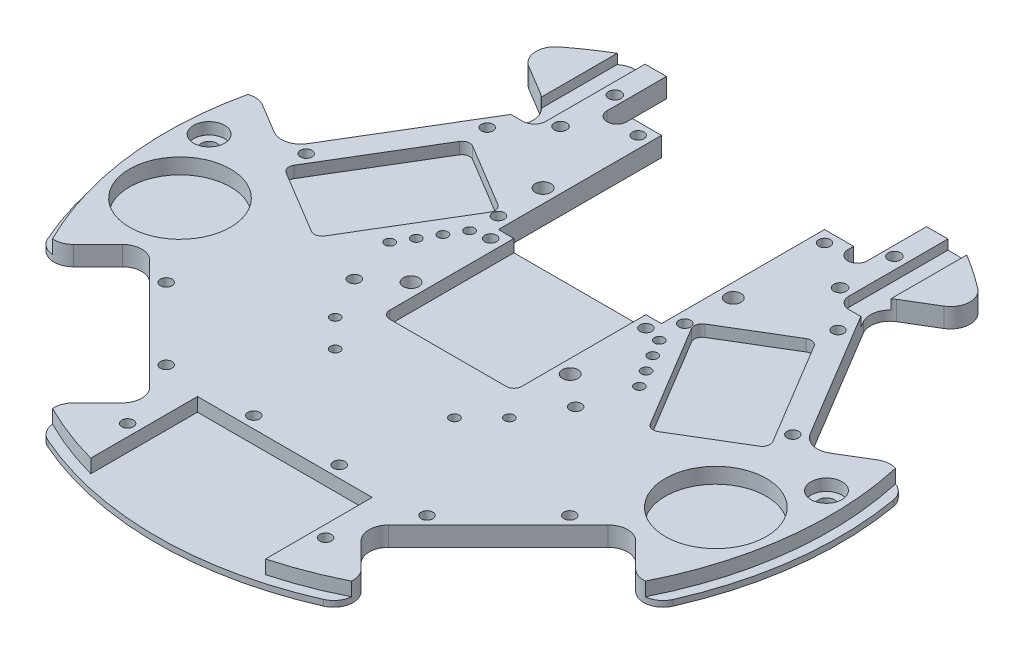
SolidWorks part; units mm, degrees
material "7079 Alloy"
ref_plane "Front" through (0, 0, 0) normal (0, 0, 1) x (1, 0, 0)
ref_plane "Top" through (0, 0, 0) normal (0, 1, 0) x (1, 0, 0)
ref_plane "Right" through (0, 0, 0) normal (1, 0, 0) x (0, 0, -1)
sketch "Sketch1" plane through (0, 0, 0) normal (0, 1, 0) x (1, 0, 0)
  line L0 (0, 0) -> (88, 0)
  line L1 (0, 88) -> (0, 0)
  line L2 (-88, 0) -> (0, 0)
  line L3 (0, -88) -> (0, 0)
  line L4 (0, 0) -> (62.2254, -62.2254)
  line L5 (0, 0) -> (-62.2254, -62.2254)
  line L6 (0, 0) -> (75.4307, 45.3234)
  line L7 (0, 0) -> (-75.4307, 45.3234)
  line L8 (59.4468, 64.8851) -> (41.5542, 54.1341)
  line L9 (41.5542, 54.1341) -> (67.3061, 11.2757)
  line L10 (67.3061, 11.2757) -> (85.1987, 22.0267)
  line L11 (77.3392, -41.9839) -> (62.579, -27.2236)
  line L12 (62.579, -27.2236) -> (27.2236, -62.579)
  line L13 (27.2236, -62.579) -> (41.9839, -77.3392)
  line L14 (-41.9839, -77.3392) -> (-27.2236, -62.579)
  line L15 (-27.2236, -62.579) -> (-62.579, -27.2236)
  line L16 (-62.579, -27.2236) -> (-77.3392, -41.9839)
  line L17 (-85.1987, 22.0267) -> (-67.3061, 11.2757)
  line L18 (-67.3061, 11.2757) -> (-41.5542, 54.1341)
  line L19 (-41.5542, 54.1341) -> (-59.4468, 64.8851)
  line L20 (-59.4468, 64.8851) -> (7.3885, 64.8851)
  line L21 (7.3885, 64.8851) -> (59.4468, 64.8851)
  line L22 (-41.5542, 54.1341) -> (0, 54.1341)
  line L23 (0, 54.1341) -> (41.5542, 54.1341)
  line L24 (41.5542, 54.1341) -> (41.5542, 77.5709)
  line L25 (-41.5542, 77.5709) -> (0, 77.5709)
  line L26 (-41.5542, 77.5709) -> (-41.5542, 54.1341)
  line L27 (0, 77.5709) -> (41.5542, 77.5709)
  circle A0 centre (0, 0) radius 88
  dimension "D1" = 176
  dimension "D2" = 31
  dimension "D3" = 31
  dimension "D4" = 45
  dimension "D5" = 24.5
  dimension "D6" = 24.5
  dimension "D7" = 24.5
  dimension "D8" = 24.5
  dimension "D9" = 25
  dimension "D10" = 25
  dimension "D11" = 25
  dimension "D12" = 25
  dimension "D13" = 25
  dimension "D14" = 25
  dimension "D15" = 25
  dimension "D16" = 25
sketch "Sketch2" plane through (0, 0, 0) normal (0, 1, 0) x (1, 0, 0)
  line L0 (85.1987, 22.0267) -> (67.3061, 11.2757)
  line L1 (67.3061, 11.2757) -> (41.5542, 54.1341)
  line L2 (77.3392, -41.9839) -> (62.579, -27.2236)
  line L3 (62.579, -27.2236) -> (27.2236, -62.579)
  line L4 (27.2236, -62.579) -> (41.9839, -77.3392)
  line L5 (-41.9839, -77.3392) -> (-27.2236, -62.579)
  line L6 (-27.2236, -62.579) -> (-62.579, -27.2236)
  line L7 (-62.579, -27.2236) -> (-77.3392, -41.9839)
  line L8 (-85.1987, 22.0267) -> (-67.3061, 11.2757)
  line L9 (-67.3061, 11.2757) -> (-41.5542, 54.1341)
  line L10 (-43, 76.7789) -> (43, 76.7789)
  line L15 (-41.5542, 54.1341) -> (-59.4468, 64.8851)
  line L16 (0, 0) -> (0, 111.6496) construction
  line L17 (41.5542, 54.1341) -> (59.4468, 64.8851)
  line L18 (-43, 76.7789) -> (43, 76.7789) construction
  arc A0 (85.1987, 22.0267) -> (77.3392, -41.9839) centre (0, 0) cw
  arc A1 (41.9839, -77.3392) -> (-41.9839, -77.3392) centre (0, 0) cw
  arc A2 (-77.3392, -41.9839) -> (-85.1987, 22.0267) centre (0, 0) cw
  arc A3 (-43, 76.7789) -> (-59.4468, 64.8851) centre (0, 0) ccw
  arc A4 (59.4468, 64.8851) -> (43, 76.7789) centre (0, 0) ccw
  dimension "D2" = 86
extrude "Extrude1" add sketch "Sketch2" against normal blind 5
sketch "Sketch3" plane through (0, 0, 0) normal (0, 1, 0) x (1, 0, 0)
  line L0 (-21, 76.7789) -> (-21, 21)
  line L1 (-21, 21) -> (21, 21)
  line L2 (21, 21) -> (21, 76.7789)
  line L3 (43, 76.7789) -> (-43, 76.7789) construction
  line L5 (-21, 76.7789) -> (21, 76.7789)
  dimension "D1" = 21
  dimension "D2" = 21
  dimension "D3" = 21
extrude "Extrude2" cut sketch "Sketch3" against normal up to surface (5 mm away) up to face at (0, -5, -1.5971)
sketch "Sketch4" plane through (0, 0, 0) normal (0, 1, 0) x (-1, 0, 0)
  line L0 (17, 13) -> (17, -27)
  line L2 (17, 13) -> (-17, 13)
  line L3 (17, -27) -> (-17, -27)
  line L4 (-17, -27) -> (-17, 13)
  line L5 (21, -21) -> (-21, -21) construction
  dimension "D1" = 34
  dimension "D2" = 17
  dimension "D3" = 34
  dimension "D4" = 40
extrude "Extrude3" cut sketch "Sketch4" against normal blind 3.2
sketch "Sketch5" plane through (0, 0, 0) normal (0, 1, 0) x (1, 0, 0)
  line L0 (42.9633, -4.5175) -> (62.6781, 7.3283)
  line L1 (62.6781, 7.3283) -> (44.6518, 37.3292)
  line L2 (44.6518, 37.3292) -> (24.9369, 25.4833)
  line L3 (24.9369, 25.4833) -> (42.9633, -4.5175)
  line L5 (67.3061, 11.2757) -> (41.5542, 54.1341) construction
  line L6 (85.1987, 22.0267) -> (67.3061, 11.2757) construction
  dimension "D1" = 6
  dimension "D2" = 35
  dimension "D3" = 23
  dimension "D4" = 1
extrude "Extrude4" cut sketch "Sketch5" against normal blind 3
mirror "Mirror1" about plane through (0, 0, 0) normal (1, 0, 0) of "Extrude4"
sketch "Sketch6" plane through (0, 0, 0) normal (0, 1, 0) x (1, 0, 0)
  line L0 (0, 0) -> (75.4307, 45.3234) construction
  line L1 (41.5542, 54.1341) -> (67.3061, 11.2757) construction
  line L2 (62.579, -27.2236) -> (27.2236, -62.579) construction
  line L3 (0, 0) -> (62.2254, -62.2254) construction
  circle A0 centre (45.1631, 42.303) radius 1.5
  circle A1 centre (62.6744, 13.1593) radius 1.5
  circle A2 centre (51.9723, -33.5876) radius 1.5
  circle A3 centre (33.5876, -51.9723) radius 1.5
  dimension "D1" = 3
  dimension "D2" = 3
  dimension "D3" = 3
  dimension "D4" = 3
  dimension "D6" = 3
  dimension "D8" = 3
  dimension "D9" = 3
  dimension "D10" = 13
  dimension "D11" = 13
  dimension "D12" = 3
  dimension "D5" = 13
  dimension "D7" = 21
extrude "Extrude5" cut sketch "Sketch6" against normal up to surface (5 mm away) up to face at (0, -5, -10.1957)
mirror "Mirror2" about plane through (0, 0, 0) normal (1, 0, 0) of "Extrude5"
sketch "Sketch7" plane through (0, 0, 0) normal (0, 1, 0) x (-1, 0, 0)
  line L1 (-21, -21) -> (-21, -76.7789) construction
  line L2 (-17, -21) -> (-21, -21) construction
  circle A0 centre (-24, -60) radius 1.5
  circle A1 centre (-24, -24) radius 1.5
  dimension "D2" = 3
  dimension "D3" = 3
  dimension "D4" = 3
  dimension "D5" = 3
  dimension "D6" = 3
  dimension "D1" = 36
extrude "Extrude6" cut sketch "Sketch7" against normal up to surface (5 mm away) up to face at (-51.9723, -5, 32.0876)
mirror "Mirror3" about plane through (0, 0, 0) normal (1, 0, 0) of "Extrude6"
sketch "Sketch8" plane through (0, 0, 0) normal (0, 1, 0) x (1, 0, 0)
  line L0 (33.5, 68.7344) -> (33.5, 63)
  line L6 (33.5, 63) -> (21, 63)
  line L7 (21, 21) -> (21, 76.7789) construction
  line L8 (21, 63) -> (21, 76.7789)
  line L9 (21, 76.7789) -> (33.5, 76.7789)
  line L10 (43, 76.7789) -> (21, 76.7789) construction
  line L11 (33.5, 76.7789) -> (33.5, 68.7344)
  circle A0 centre (24, 60) radius 1.5 construction
  dimension "D4" = 3
extrude "Extrude7" cut sketch "Sketch8" against normal up to surface (5 mm away) up to face at (-24, -5, -61.5)
mirror "Mirror4" about plane through (0, 0, 0) normal (1, 0, 0) of "Extrude7"
sketch "Sketch9" plane through (0, 0, 0) normal (0, 1, 0) x (1, 0, 0)
  line L5 (33.5, 63) -> (33.5, 76.7789) construction
  circle A0 centre (36, 66) radius 1.6
  circle A1 centre (36, 52) radius 1.6
  dimension "D1" = 3.2
  dimension "D2" = 3.2
  dimension "D3" = 52
  dimension "D4" = 66
  dimension "D5" = 2.5
extrude "Extrude8" cut sketch "Sketch9" against normal up to surface (5 mm away) up to face at (-24, -5, -61.5)
mirror "Mirror5" about plane through (0, 0, 0) normal (1, 0, 0) of "Extrude8"
fillet "Fillet2" radius 2 10 edges at (-17, -1.6, 13) (17, -1.6, 13) (-42.9633, -1.5, 4.5175) (-24.9369, -1.5, -25.4833) (-44.6518, -1.5, -37.3292) (-62.6781, -1.5, -7.3283) (42.9633, -1.5, 4.5175) (24.9369, -1.5, -25.4833) (44.6518, -1.5, -37.3292) (62.6781, -1.5, -7.3283)
fillet "Fillet3" radius 5 16 edges at (59.4468, -2.5, -64.8851) (41.5542, -2.5, -54.1341) (67.3061, -2.5, -11.2757) (85.1987, -2.5, -22.0267) (77.3392, -2.5, 41.9839) (62.579, -2.5, 27.2236) (27.2236, -2.5, 62.579) (41.9839, -2.5, 77.3392) (-27.2236, -2.5, 62.579) (-41.9839, -2.5, 77.3392) (-62.579, -2.5, 27.2236) (-77.3392, -2.5, 41.9839) (-85.1987, -2.5, -22.0267) (-67.3061, -2.5, -11.2757) (-41.5542, -2.5, -54.1341) (-59.4468, -2.5, -64.8851)
fillet "Fillet4" radius 5 2 edges at (43, -2.5, -76.7789) (-43, -2.5, -76.7789)
sketch "Sketch11" plane through (0, 0, 0) normal (0, 1, 0) x (1, 0, 0)
  line L3 (-21, 21) -> (-21, 63) construction
  line L4 (21, 21) -> (21, 63) construction
  circle A2 centre (24.5, 36) radius 2
  circle A3 centre (-24.5, 36) radius 2
  dimension "D7" = 4
  dimension "D8" = 4
  dimension "D9" = 3.5
  dimension "D10" = 3.5
extrude "Extrude10" cut sketch "Sketch11" against normal up to surface (5 mm away) up to face at (-36, -5, -67.6)
sketch "Sketch14" plane through (0, 0, 0) normal (0, 1, 0) x (1, 0, 0)
  line L0 (25.967, 23.769) -> (41.9332, -2.8032) construction
  line L1 (42.9374, 36.2991) -> (26.6513, 26.5134) construction
  line L2 (25.967, 23.769) -> (41.9332, -2.8032) construction
  line L5 (64.7309, 15.5616) -> (44.1294, 49.8483) construction
  line L6 (30.7591, -59.0434) -> (59.0434, -30.7591) construction
  line L7 (66.1145, -30.7591) -> (72.3997, -37.0444) construction
  circle A0 centre (24.4364, 17.0161) radius 1.25
  circle A1 centre (29.5867, 8.4444) radius 1.25
  circle A2 centre (22.4224, -19.5939) radius 1.25
  circle A3 centre (15.3513, -26.665) radius 1.25
  circle A4 centre (27.0116, 12.7303) radius 1.25
  circle A5 centre (32.1619, 4.1586) radius 1.25
  dimension "D1" = 2.5
  dimension "D3" = 7
  dimension "D4" = 2.5
  dimension "D7" = 33.79
  dimension "D9" = 2.5
  dimension "D10" = 33.79
  dimension "D12" = 10
  dimension "D8" = 2.5
  dimension "D14" = 2.5
  dimension "D16" = 2.5
  dimension "D2" = 4.79
  dimension "D5" = 4.79
  dimension "D6" = 10
  dimension "D11" = 33.79
  dimension "D13" = 23
  dimension "D15" = 5
  dimension "D17" = 5
  dimension "D18" = 4.79
  dimension "D19" = 4.79
sketch "Sketch15" plane through (0, 0, 0) normal (0, 1, 0) x (1, 0, 0)
  circle A0 centre (69, -13) radius 13
  dimension "D1" = 26
  dimension "D2" = 13
  dimension "D3" = 69
extrude "Extrude13" cut sketch "Sketch15" against normal blind 4
mirror "Mirror7" about plane through (0, 0, 0) normal (1, 0, 0) of "Extrude13"
sketch "Sketch16" plane through (0, 0, 0) normal (0, 1, 0) x (1, 0, 0)
  line L1 (-22.5, -55) -> (22.5, -55)
  line L2 (-22.5, -55) -> (-22.5, -95)
  line L3 (-22.5, -95) -> (22.5, -95)
  line L4 (22.5, -55) -> (22.5, -95)
  dimension "D1" = 22.5
  dimension "D2" = 22.5
  dimension "D3" = 55
  dimension "D4" = 40
extrude "Extrude14" cut sketch "Sketch16" against normal blind 3.5
sketch "Sketch17" plane through (0, 0, 0) normal (0, 1, 0) x (1, 0, 0)
  line L0 (22.5, -85.075) -> (22.5, -55) construction
  line L1 (-22.5, -55) -> (-22.5, -85.075) construction
  circle A0 centre (25.5, -70) radius 1.5
  circle A1 centre (-25.5, -70) radius 1.5
  dimension "D1" = 3
  dimension "D2" = 3
  dimension "D3" = 3
  dimension "D4" = 3
  dimension "D5" = 70
extrude "Extrude16" cut sketch "Sketch17" against normal up to surface (5 mm away) up to face at (-24.5, -5, -38)
sketch "Sketch18" plane through (0, 0, 0) normal (0, 1, 0) x (-1, 0, 0)
  line L0 (-22.5, 55) -> (22.5, 55) construction
  line L1 (-22.5, 55) -> (22.5, 55) construction
  circle A0 centre (-11, 52) radius 1.5
  circle A1 centre (11, 52) radius 1.5
  dimension "D1" = 3
  dimension "D2" = 3
  dimension "D3" = 3
  dimension "D4" = 3
  dimension "D5" = 11
  dimension "D6" = 11
extrude "Extrude17" cut sketch "Sketch18" against normal up to surface (5 mm away) up to face at (-25.5, -5, 68.5)
sketch "Sketch20" plane through (0, 0, 0) normal (0, 1, 0) x (1, 0, 0)
  circle A0 centre (20.5, -2) radius 2
  circle A1 centre (-20.5, -2) radius 2
  dimension "D1" = 4
  dimension "D2" = 4
  dimension "D3" = 20.5
  dimension "D4" = 20.5
  dimension "D5" = 2
  dimension "D6" = 2
extrude "Extrude19" cut sketch "Sketch20" against normal up to surface (5 mm away) up to face at (-11, -5, 50.5)
sketch "Sketch27" plane through (0, 0, 0) normal (0, 1, 0) x (1, 0, 0)
  line L1 (17, 21) -> (21, 21) construction
  line L2 (17, -11) -> (17, 21) construction
  line L3 (-17, 21) -> (-17, -11) construction
  circle A0 centre (20, 18) radius 1.5
  circle A1 centre (-20, 18) radius 1.5
  dimension "D1" = 3
  dimension "D2" = 3
  dimension "D4" = 3
  dimension "D3" = 3
  dimension "D5" = 3
extrude "Extrude26" cut sketch "Sketch27" against normal up to surface (5 mm away) up to face at (-20.5, -5, 0)
sketch "Sketch28" plane through (0, 0, 0) normal (0, 1, 0) x (1, 0, 0)
  circle A0 centre (28.5, -8.6) radius 1.5
  circle A1 centre (11, -52) radius 1.5 construction
  circle A2 centre (-28.5, -8.6) radius 1.5
  circle A3 centre (-11, -52) radius 1.5 construction
  dimension "D2" = 17.5
  dimension "D3" = 3
  dimension "D5" = 3
  dimension "D1" = 43.4
  dimension "D4" = 17.5
extrude "Extrude27" cut sketch "Sketch28" against normal up to surface (5 mm away) up to face at (-20, -5, -19.5)
sketch "Sketch29" plane through (0, 0, 0) normal (0, 1, 0) x (1, 0, 0)
  circle A0 centre (-79.5, 5) radius 4
  circle A1 centre (79.5, 5) radius 4
  dimension "D2" = 79.5
  dimension "D4" = 8
  dimension "D5" = 8
  dimension "D1" = 5
  dimension "D3" = 79.5
extrude "Extrude28" cut sketch "Sketch29" against normal blind 3
sketch "Sketch30" plane through (0, -3, 0) normal (0, 1, 0) x (1, 0, 0)
  circle A0 centre (79.5, 5) radius 2
  circle A1 centre (-79.5, 5) radius 2
  dimension "D1" = 4
  dimension "D2" = 4
extrude "Extrude29" cut sketch "Sketch30" against normal up to surface (2 mm away) up to face at (-28.5, -5, 7.1)
extrude "Extrude30" cut sketch "Sketch14" against normal up to surface (5 mm away) up to face at (-79.5, -5, -7)
mirror "Mirror9" about plane through (0, 0, 0) normal (1, 0, 0) of "Extrude30"
sketch "Sketch31" plane through (0, 0, 0) normal (0, 1, 0) x (1, 0, 0)
  line L0 (-74.1867, 42.5039) -> (-76.3559, 43.7467)
  line L2 (74.1867, 42.5039) -> (76.3559, 43.7467)
  arc A0 (-74.1867, 42.5039) -> (74.1867, 42.5039) centre (0, 0) ccw
  arc A1 (-76.3559, 43.7467) -> (76.3559, 43.7467) centre (0, 0) ccw
  dimension "D1" = 171
extrude "Cut-Extrude1" cut sketch "Sketch31" against normal blind 3.5
sketch "Sketch33" plane through (0, 0, 0) normal (0, 1, 0) x (1, 0, 0)
  line L0 (-39, 76.7789) -> (-45, 76.7789)
  line L3 (-33.5, 76.7789) -> (-41.6748, 76.7789) construction
  line L4 (-45, 76.7789) -> (-45, 48.2789)
  line L9 (-45, 48.2789) -> (-39, 48.2789)
  line L10 (-39, 48.2789) -> (-39, 76.7789)
  line L11 (0, 0) -> (0, 104.2822) construction
  line L12 (39, 48.2789) -> (39, 76.7789)
  line L13 (45, 48.2789) -> (39, 48.2789)
  line L14 (45, 76.7789) -> (45, 48.2789)
  line L15 (39, 76.7789) -> (45, 76.7789)
  dimension "D1" = 5.5
  dimension "D2" = 6
  dimension "D3" = 28.5
extrude "Cut-Extrude3" cut sketch "Sketch33" against normal blind 2.5
fillet "Fillet5" radius 3 2 edges at (39, -1.25, -48.2789) (-39, -1.25, -48.2789)
sketch "Sketch34" plane through (0, 0, 0) normal (0, 1, 0) x (1, 0, 0)
  line L0 (-33.5, 63) -> (-33.5, 59)
  line L1 (-33.5, 59) -> (-28.5, 59)
  line L2 (-28.5, 59) -> (-28.5, 63)
  line L4 (-21, 63) -> (-33.5, 63) construction
  line L5 (-28.5, 63) -> (-33.5, 63)
  line L6 (0, 0) -> (0, 90.7879) construction
  line L7 (28.5, 63) -> (33.5, 63)
  line L8 (28.5, 59) -> (28.5, 63)
  line L9 (33.5, 59) -> (28.5, 59)
  line L10 (33.5, 63) -> (33.5, 59)
  dimension "D1" = 4
  dimension "D2" = 5
extrude "Cut-Extrude4" cut sketch "Sketch34" against normal blind 10
fillet "Fillet6" radius 2.5 4 edges at (28.5, -2.5, -59) (33.5, -2.5, -59) (-28.5, -2.5, -59) (-33.5, -2.5, -59)
